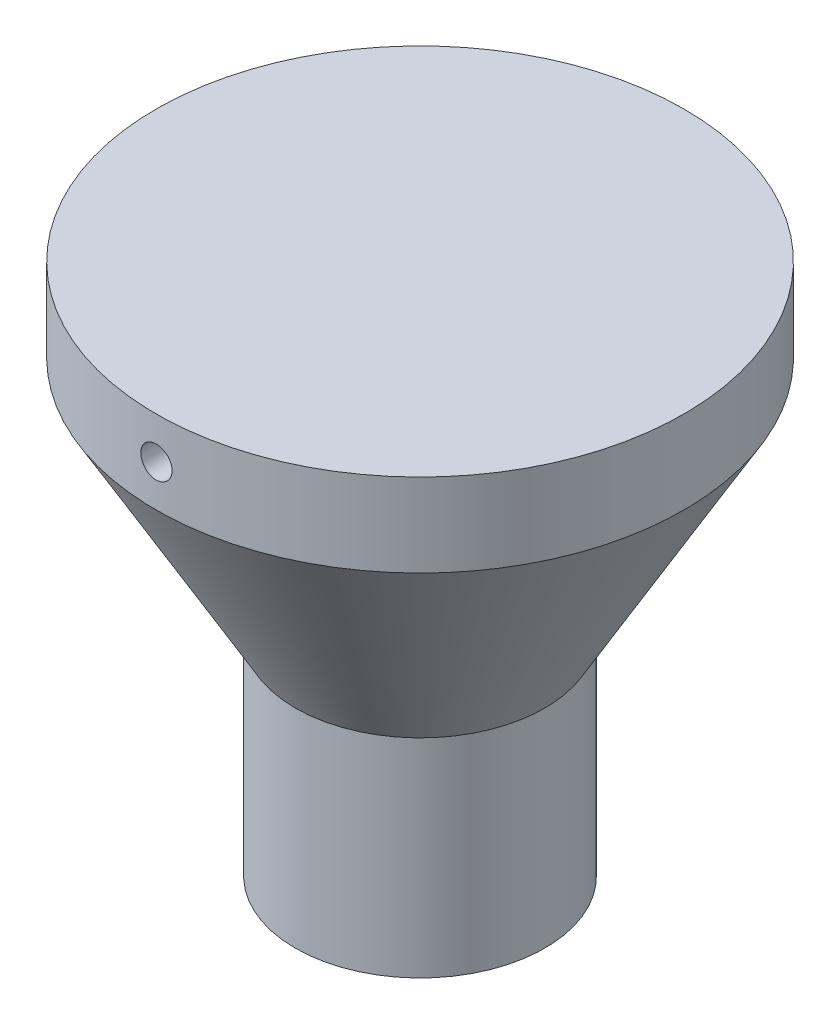
SolidWorks part; units mm, degrees
ref_plane "Front Plane" through (0, 0, 0) normal (0, 0, 1) x (1, 0, 0)
ref_plane "Top Plane" through (0, 0, 0) normal (0, 1, 0) x (1, 0, 0)
ref_plane "Right Plane" through (0, 0, 0) normal (1, 0, 0) x (0, 0, -1)
sketch "Sketch1" plane through (0, 0, 0) normal (0, 0, 1) x (1, 0, 0)
  line L0 (0, 0) -> (0, 88)
  line L1 (0, 0) -> (-30, 0)
  line L2 (-30, 0) -> (-30, 50)
  line L3 (-30, 50) -> (-63.4863, 108)
  line L5 (-63.4863, 108) -> (-63.4863, 128)
  line L6 (-63.4863, 128) -> (0, 128)
  line L7 (0, 128) -> (0, 88)
  line L8 (-30, 50) -> (0, 50)
  dimension "D1" = 88
  dimension "D2" = 30
  dimension "D3" = 50
  dimension "D4" = 150
  dimension "D5" = 20
  dimension "D6" = 63.4863
revolve "Revolve1" add sketch "Sketch1" angle 360 about L0 region at (-26.7225, 93.7976, 0)
shell "Shell1" thickness 10 removed face at (0, 50, -30)
sketch "Sketch4" plane through (0, 0, 0) normal (0, 0, 1) x (1, 0, 0)
  line L0 (0, 128) -> (0, 108) construction
  line L1 (63.4863, 128) -> (-63.4863, 128) construction
  line L2 (63.4863, 108) -> (-63.4863, 108) construction
  circle A0 centre (0, 118) radius 3.75
  dimension "D1" = 7.5
extrude "Cut-Extrude2" cut sketch "Sketch4" against normal mid plane 150
revolve "Revolve2" add sketch "Sketch1<3>" angle 360 about L0 region at (-15, 25, 0)
sketch "Sketch1<3>" plane through (0, 0, 0) normal (0, 0, 1) x (1, 0, 0) same geometry as "Sketch1"
shell "Shell3" thickness 12 removed face at (0, 0, -30) removed face at (0, 50, 18.453)
sketch "Sketch5" plane through (0, 0, 0) normal (0, -1, 0) x (1, 0, 0)
  circle A0 centre (0, 0) radius 20.5
  circle A1 centre (0, 0) radius 25
  dimension "D1" = 41
  dimension "D2" = 50
extrude "Cut-Extrude3" cut sketch "Sketch5" against normal blind 2.5
